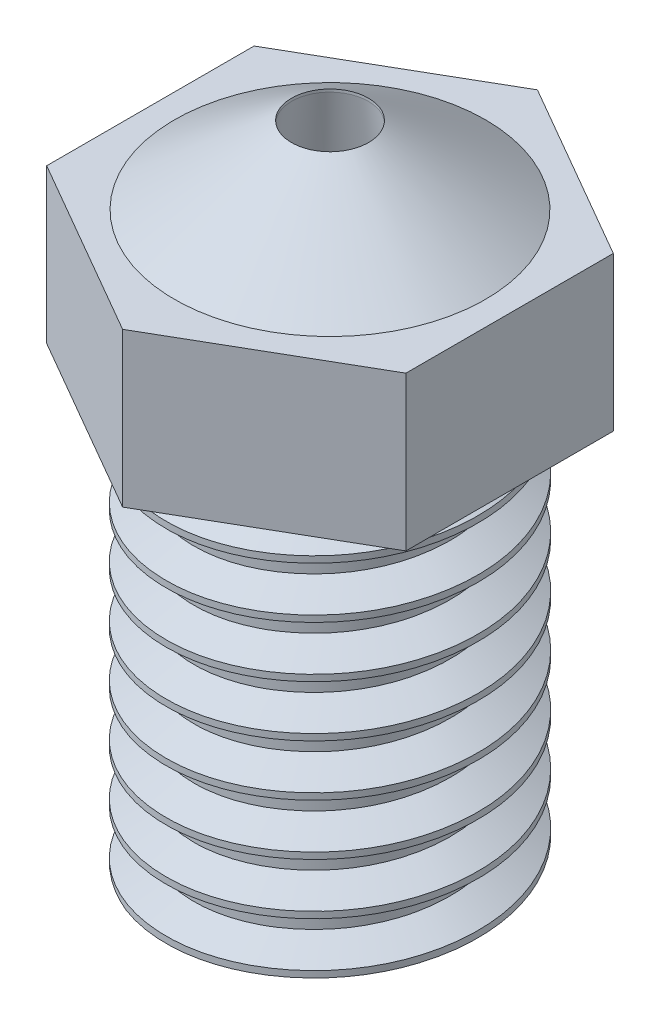
SolidWorks part; units mm, degrees
ref_plane "Front Plane" through (0, 0, 0) normal (0, 0, 1) x (1, 0, 0)
ref_plane "Top Plane" through (0, 0, 0) normal (0, 1, 0) x (1, 0, 0)
ref_plane "Right Plane" through (0, 0, 0) normal (1, 0, 0) x (0, 0, -1)
sketch "Sketch1" plane through (0, 0, 0) normal (0, 1, 0) x (1, 0, 0)
  circle A0 centre (0, 0) radius 2.5
  dimension "D1" = 5
extrude "Boss-Extrude1" add sketch "Sketch1" along normal blind 8 contours A0
sketch "Sketch9" plane through (0, 8, 0) normal (0, 1, 0) x (1, 0, 0)
  line L1 (3.5, 2.0207) -> (0, 4.0415)
  line L2 (0, 4.0415) -> (-3.5, 2.0207)
  line L3 (-3.5, 2.0207) -> (-3.5, -2.0207)
  line L4 (-3.5, -2.0207) -> (0, -4.0415)
  line L5 (0, -4.0415) -> (3.5, -2.0207)
  line L6 (3.5, -2.0207) -> (3.5, 2.0207)
  circle A0 centre (0, 0) radius 3.5 construction
  dimension "D1" = 7
extrude "Boss-Extrude2" add sketch "Sketch9" along normal blind 3 contours L3 L4 L5 L6 L1 L2
sketch "Sketch10" plane through (0, 0, 0) normal (1, 0, 0) x (0, 0, -1)
  line L0 (0, 11) -> (0, 13) construction
  line L1 (-2.0207, 11) -> (2.0207, 11) construction
  line L2 (0, 13) -> (3.0311, 11)
  line L3 (2.0207, 11) -> (4.0415, 11) construction
  line L4 (3.0311, 11) -> (0, 11)
  line L5 (0, 11) -> (0, 13)
  dimension "D1" = 2
revolve "Revolve1" add sketch "Sketch10" angle 360 about L0
sketch "Sketch11" plane through (0, 0, 0) normal (0, -1, 0) x (1, 0, 0)
  circle A0 centre (0, 0) radius 0.75
  dimension "D1" = 1.5
extrude "Cut-Extrude1" cut sketch "Sketch11" against normal through all
thread "Thread1" pitch 1 method extrude trim with start face yes trim with end face yes profile "Thread Profile2" start angle 0, offset 1, length 0, pitch 1, diameter 5
ref_plane "Plane2" through (2.5, -1, 0) normal (0, 0, 1) x (1, 0, 0)
sketch "Thread Profile2" plane through (2.5, -1, 0) normal (0, 0, 1) x (1, 0, 0)
  line L0 (0, 0) -> (0, 1) construction
  line L1 (0, 0) -> (0.5413, 0.3125)
  line L2 (0.5413, 0.3125) -> (0.5413, 0.4375)
  line L3 (0.5413, 0.4375) -> (0, 0.75)
  line L4 (0.5413, 0.375) -> (0, 0.375) construction
  line L11 (0, 0) -> (0, 0.75)
  point P2 (0, 0)
  dimension "Pitch" = 1
  dimension "Profile_Angle" = 60
  dimension "Profile_Land" = 0.125
  dimension "Profile_Height" = 0.5413
sketch "Esboço1" plane through (0, 0, 0) normal (0, -1, 0) x (1, 0, 0)
  circle A0 centre (0, 0) radius 2.5
  dimension "D1" = 5
extrude "Corte-extrusão1" cut sketch "Esboço1" against normal through all draft 8
